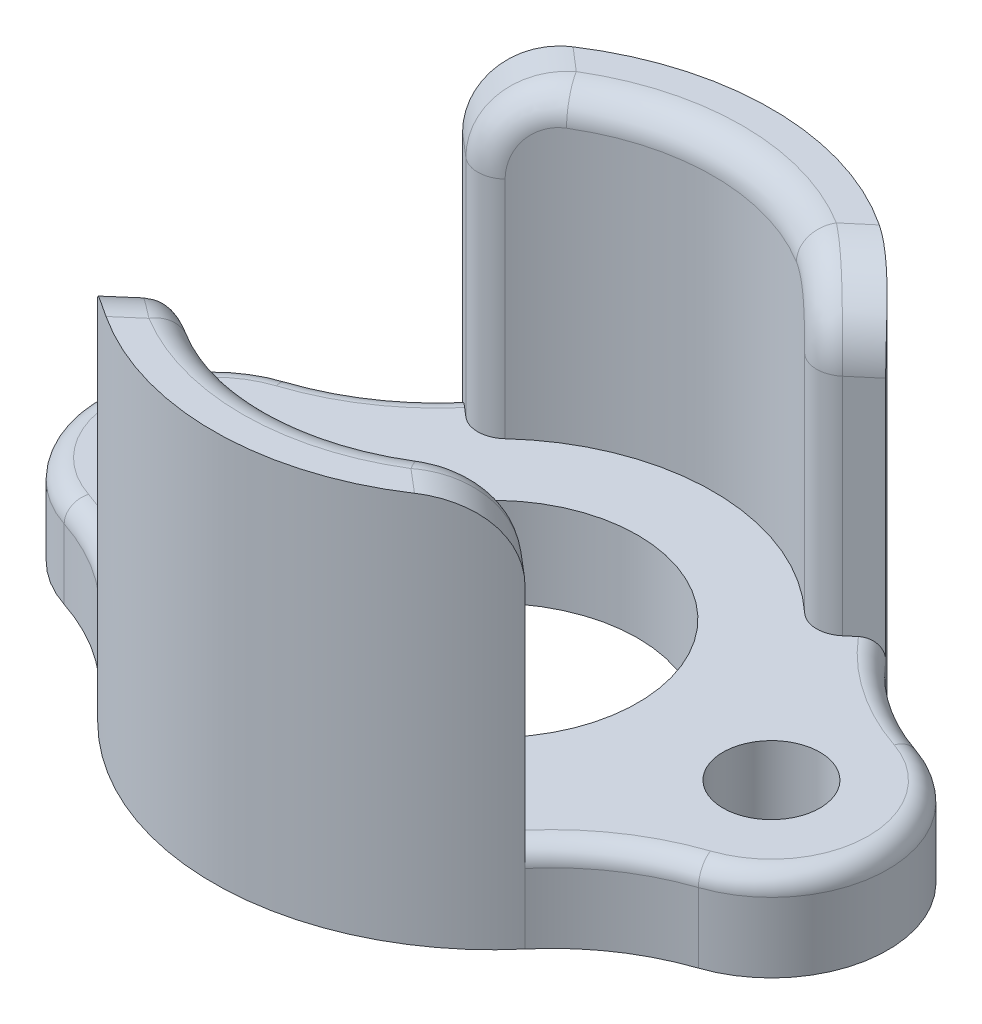
SolidWorks part; units mm, degrees
ref_plane "Front Plane" through (0, 0, 0) normal (0, 0, 1) x (1, 0, 0)
ref_plane "Top Plane" through (0, 0, 0) normal (0, 1, 0) x (1, 0, 0)
ref_plane "Right Plane" through (0, 0, 0) normal (1, 0, 0) x (0, 0, -1)
sketch "Sketch1" plane through (0, 0, 0) normal (0, 1, 0) x (1, 0, 0)
  line L0 (10.2, 0) -> (-10.25, 0) construction
  line L1 (0, 0) -> (0, 14.0423) construction
  arc A0 (-6.554, -2.9808) -> (6.575, -2.9342) centre (0, 0) ccw
  arc A1 (-6.554, 2.9808) -> (-6.554, -2.9808) centre (-7.2, 0) ccw
  arc A2 (6.575, -2.9342) -> (6.575, 2.9342) centre (7.2, 0) ccw
  arc A3 (6.575, 2.9342) -> (-6.554, 2.9808) centre (0, 0) ccw
  dimension "D1" = 7.2
  dimension "D2" = 20.45
  dimension "D3" = 14.4
  dimension "D4" = 3
extrude "Boss-Extrude1" add sketch "Sketch1" along normal blind 2.3
fillet "Fillet1" radius 6 4 edges at (6.575, 1.15, -2.9342) (6.575, 1.15, 2.9342) (-6.554, 1.15, 2.9808) (-6.554, 1.15, -2.9808)
sketch "Sketch2" plane through (0, 2.3, 0) normal (0, 1, 0) x (1, 0, 0)
  circle A0 centre (0, 0) radius 3.75
  dimension "D1" = 7.5
extrude "Cut-Extrude1" cut sketch "Sketch2" against normal up to surface (2.3 mm away) up to face at (0.0058, 0, 0)
sketch "Sketch3" plane through (0, 2.3, 0) normal (0, 1, 0) x (1, 0, 0)
  line L0 (-4.3235, 3.7145) -> (-5.4613, 4.692)
  line L1 (4.3506, 3.6827) -> (5.4955, 4.6519)
  line L2 (4.3506, -3.6827) -> (5.4955, -4.6519)
  line L3 (-4.3235, -3.7145) -> (-5.4613, -4.692)
  arc A0 (5.4955, 4.6519) -> (-5.4613, 4.692) centre (0, 0) ccw construction
  arc A1 (-5.4613, -4.692) -> (5.4955, -4.6519) centre (0, 0) ccw construction
  arc A2 (5.4955, 4.6519) -> (-5.4613, 4.692) centre (0, 0) ccw
  arc A3 (-5.4613, -4.692) -> (5.4955, -4.6519) centre (0, 0) ccw
  arc A4 (4.3506, 3.6827) -> (-4.3235, 3.7145) centre (0, 0) ccw
  arc A5 (-4.3235, -3.7145) -> (4.3506, -3.6827) centre (0, 0) ccw
  dimension "D1" = 1.5
extrude "Boss-Extrude2" add sketch "Sketch3" along normal blind 7.8
sketch "Sketch4" plane through (0, 2.3, 0) normal (0, 1, 0) x (1, 0, 0)
  circle A0 centre (-7.2, 0) radius 1.25
  circle A1 centre (7.2, 0) radius 1.25
  dimension "D1" = 2.5
extrude "Cut-Extrude2" cut sketch "Sketch4" against normal up to surface (2.3 mm away) up to face at (0, 0, 3.75)
fillet "Fillet2" radius 2 4 edges at (-4.8924, 10.1, 4.2032) (4.923, 10.1, 4.1673) (4.923, 10.1, -4.1673) (-4.8924, 10.1, -4.2032)
fillet "Fillet3" radius 0.75 10 edges at (4.3506, 5.2, 3.6827) (3.8014, 9.6892, 4.2473) (0.0209, 10.1, 5.7) (-4.0258, 9.3481, 4.0352) (4.3506, 5.2, -3.6827) (4.0552, 9.3481, -4.0056) (0.0209, 10.1, -5.7) (-3.7702, 9.6892, -4.275) (-4.3235, 5.2, 3.7145) (-4.3235, 5.2, -3.7145)
fillet "Fillet4" radius 0.5 6 edges at (6.7033, 2.3, 3.5654) (10.2, 2.3, 0) (-6.6816, 2.3, 3.6113) (-10.25, 2.3, 0) (6.7033, 2.3, -3.5654) (-6.6816, 2.3, -3.6113)
